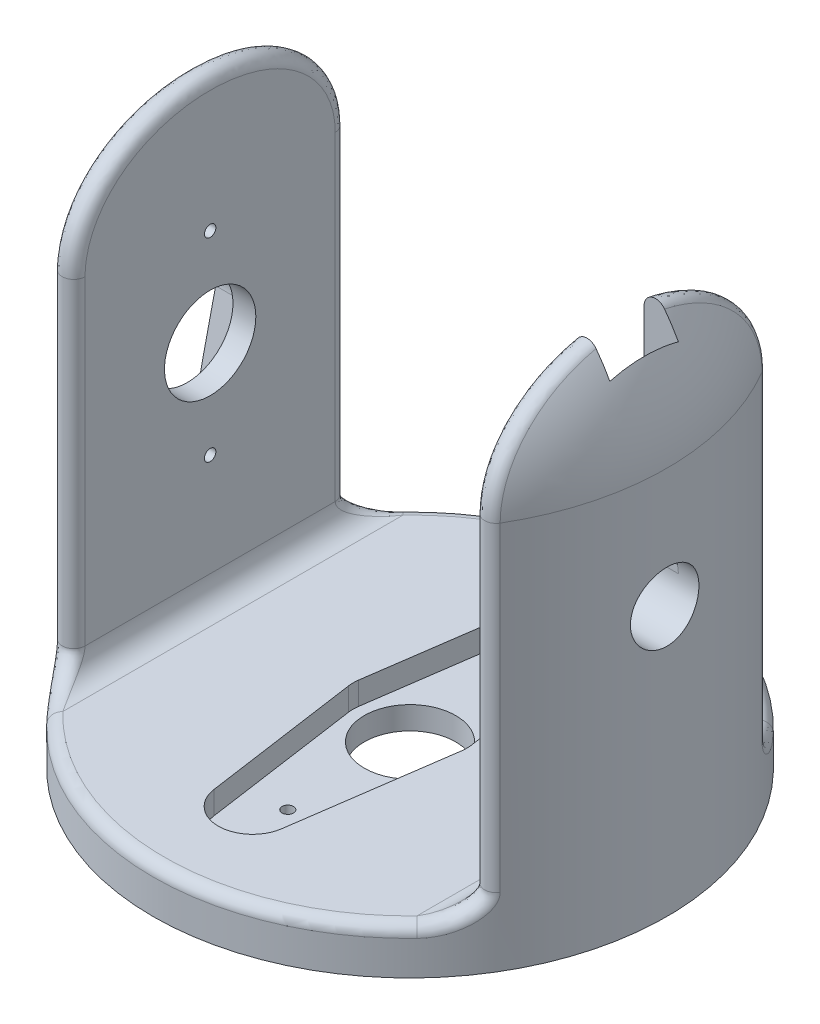
SolidWorks part; units mm, degrees
material "ABS"
ref_plane "前视基准面" through (0, 0, 0) normal (0, 0, 1) x (1, 0, 0)
ref_plane "上视基准面" through (0, 0, 0) normal (0, 1, 0) x (1, 0, 0)
ref_plane "右视基准面" through (0, 0, 0) normal (1, 0, 0) x (0, 0, -1)
sketch "草图1" plane through (0, 0, 0) normal (0, 1, 0) x (1, 0, 0)
  circle A0 centre (0, 0) radius 22.5
  dimension "D1" = 45
extrude "凸台-拉伸1" add sketch "草图1" along normal blind 4
sketch "草图2" plane through (0, 4, 0) normal (0, 1, 0) x (1, 0, 0)
  line L0 (-2.9698, 14.2111) -> (-4.9394, 0.4243)
  line L1 (-4.9394, -0.4243) -> (-2.9698, -14.2111)
  line L2 (2.9698, -14.2111) -> (4.9394, -0.4243)
  line L3 (4.9394, 0.4243) -> (2.9698, 14.2111)
  arc A0 (-2.9698, -14.2111) -> (2.9698, -14.2111) centre (0, -13.7868) ccw
  arc A1 (4.9394, -0.4243) -> (4.9394, 0.4243) centre (1.9695, 0) ccw
  arc A2 (-4.9394, 0.4243) -> (-4.9394, -0.4243) centre (-1.9695, 0) ccw
  arc A3 (-2.9698, 14.2111) -> (2.9698, 14.2111) centre (0, 13.7868) cw
  point P10 (0, -35)
  point P13 (5, 0)
  point P16 (-5, 0)
  point P19 (0, 35)
  dimension "D3" = 3
  dimension "D1" = 5
  dimension "D2" = 35
extrude "切除-拉伸1" cut sketch "草图2" against normal blind 2
sketch "草图3" plane through (0, 2, 0) normal (0, 1, 0) x (1, 0, 0)
  circle A0 centre (0, 0) radius 4
  dimension "D1" = 8
extrude "切除-拉伸2" cut sketch "草图3" against normal up to next
sketch "草图4" plane through (0, 4, 0) normal (0, 1, 0) x (1, 0, 0)
  line L0 (-17.5, 14.1421) -> (-17.5, -14.1421)
  line L1 (0, 0) -> (0, 16.7873) construction
  line L2 (17.5, 14.1421) -> (17.5, -14.1421)
  circle A0 centre (0, 0) radius 22.5 construction
  arc A1 (-17.5, -14.1421) -> (-17.5, 14.1421) centre (0, 0) cw
  arc A2 (17.5, -14.1421) -> (17.5, 14.1421) centre (0, 0) ccw
  dimension "D1" = 17.5
extrude "凸台-拉伸2" add sketch "草图4" along normal blind 45
sketch "草图5" plane through (-17.5, 0, 0) normal (1, 0, 0) x (0, 0, -1)
  line L0 (-1.9677, 40.1774) -> (-4.935, 23.8578)
  line L1 (-4.935, 23.1422) -> (-1.9677, 6.8226)
  line L2 (1.9677, 6.8226) -> (4.935, 23.1422)
  line L3 (4.935, 23.8578) -> (1.9677, 40.1774)
  arc A0 (-1.9677, 6.8226) -> (1.9677, 6.8226) centre (0, 7.1803) ccw
  arc A1 (-4.935, 23.8578) -> (-4.935, 23.1422) centre (-2.9672, 23.5) ccw
  arc A2 (4.935, 23.1422) -> (4.935, 23.8578) centre (2.9672, 23.5) ccw
  arc A3 (1.9677, 40.1774) -> (-1.9677, 40.1774) centre (0, 39.8197) ccw
  point P14 (0, -4)
  point P17 (-5, 23.5)
  point P20 (5, 23.5)
  point P23 (0, 51)
  dimension "D4" = 2
  dimension "D1" = 4
  dimension "D2" = 55
  dimension "D3" = 10
extrude "切除-拉伸3" cut sketch "草图5" against normal up to next
sketch "草图6" plane through (-17.5, 0, 0) normal (1, 0, 0) x (0, 0, -1)
  line L0 (0, 23.5) -> (11.6353, 23.5) construction
  line L1 (4.9672, 41.8197) -> (-4.9672, 41.8197)
  line L2 (4.9672, 41.8197) -> (4.9672, 5.1803)
  line L3 (4.9672, 5.1803) -> (-4.9672, 5.1803)
  line L4 (-4.9672, 41.8197) -> (-4.9672, 5.1803)
  arc A0 (-1.9677, 6.8226) -> (1.9677, 6.8226) centre (0, 7.1803) ccw construction
  arc A1 (-4.935, 23.8578) -> (-4.935, 23.1422) centre (-2.9672, 23.5) ccw construction
  arc A2 (4.935, 23.1422) -> (4.935, 23.8578) centre (2.9672, 23.5) ccw construction
  arc A3 (1.9677, 40.1774) -> (-1.9677, 40.1774) centre (0, 39.8197) ccw construction
  circle A4 centre (0, 23.5) radius 4
  circle A5 centre (0, 32) radius 0.5
  circle A6 centre (0, 15) radius 0.5
  point P18 (-4.9672, 23.5)
  point P19 (4.9672, 23.5)
  point P20 (0, 5.1803)
  dimension "D1" = 8
  dimension "D3" = 1
  dimension "D2" = 8.5
extrude "凸台-拉伸3" add sketch "草图6" against normal blind 2
sketch "草图7" plane through (17.5, 0, 0) normal (-1, 0, 0) x (0, 0, 1)
  circle A0 centre (0, 23.5) radius 3
  dimension "D1" = 6
extrude "切除-拉伸5" cut sketch "草图7" against normal up to next
sketch "草图8" plane through (0, 49, 0) normal (0, 1, 0) x (1, 0, 0)
  line L0 (17.5, 14.1421) -> (17.5, -14.1421) construction
  line L1 (17.5, 3) -> (20.5, 3)
  line L2 (17.5, 3) -> (17.5, -3)
  line L3 (17.5, -3) -> (20.5, -3)
  line L4 (20.5, 3) -> (20.5, -3)
  point P6 (17.5, 0)
  dimension "D1" = 3
  dimension "D2" = 6
extrude "切除-拉伸6" cut sketch "草图8" against normal up to next
fillet "圆角4" radius 2 2 edges at (17.5, 4, 0) (-17.5, 4, 0)
fillet "圆角10" radius 15 2 edges at (22.5, 49, 0) (-22.5, 49, 0)
fillet "圆角11" radius 1 13 edges at (17.5, 40.9418, -11.2368) (17.5, 20, -14.1421) (17.0152, 4.6945, -14.7219) (0, 4, -22.5) (-17.2731, 5.0748, -14.4184) (-17.5, 20, -14.1421) (-17.5, 45.1681, -0.6924) (-17.5, 20, 14.1421) (-17.0152, 4.6945, 14.7219) (17.5, 40.157, 11.9274) (17.5, 20, 14.1421) (17.2731, 5.0748, 14.4184) (0, 4, 22.5)
sketch "草图9" plane through (0, 2, 0) normal (0, 1, 0) x (1, 0, 0)
  circle A0 centre (0.2017, 10.4981) radius 0.5
  circle A1 centre (-0.2017, -10.4981) radius 0.5
extrude "切除-拉伸7" cut sketch "草图9" against normal up to next
